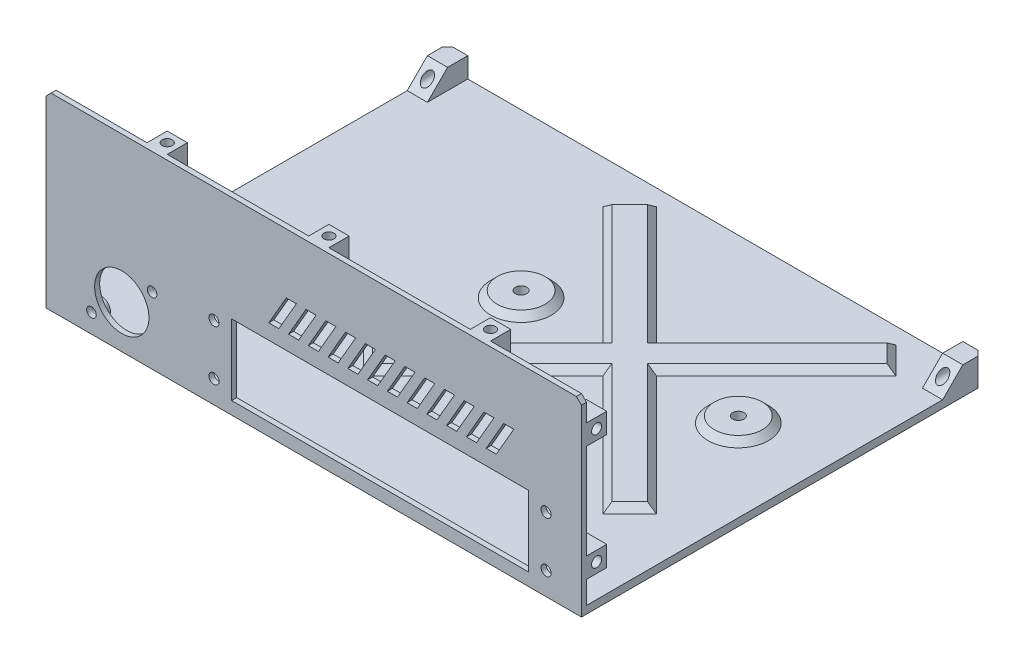
SolidWorks part; units mm, degrees
ref_plane "Płaszczyzna przednia" through (0, 0, 0) normal (0, 0, 1) x (1, 0, 0)
ref_plane "Płaszczyzna górna" through (0, 0, 0) normal (0, 1, 0) x (1, 0, 0)
ref_plane "Płaszczyzna prawa" through (0, 0, 0) normal (1, 0, 0) x (0, 0, -1)
sketch "Szkic1" plane through (0, 0, 0) normal (0, 0, 1) x (1, 0, 0)
  line L1 (0, 0) -> (212, 0)
  line L2 (0, 0) -> (0, 74.66)
  line L3 (0, 74.66) -> (212, 74.66)
  line L4 (212, 0) -> (212, 74.66)
  dimension "D1" = 212
  dimension "D2" = 74.66
extrude "Dodanie-wyciągnięcie1" add sketch "Szkic1" along normal blind 2
ref_plane "Płaszczyzna1" through (106, 0, 0) normal (1, 0, 0) x (0, 0, -1)
sketch "Szkic5" plane through (0, 0, 2) normal (0, 0, 1) x (1, 0, 0)
  line L0 (212, 74.66) -> (0, 74.66) construction
  line L1 (73.5, 33) -> (191, 33)
  line L2 (73.5, 33) -> (73.5, 5)
  line L3 (73.5, 5) -> (191, 5)
  line L4 (191, 33) -> (191, 5)
  line L5 (106, 74.66) -> (106, 105.9064) construction
  line L6 (132.25, 5) -> (132.25, 33) construction
  line L7 (0, 0) -> (212, 0) construction
  line L8 (73.5, 19) -> (191, 19) construction
  line L10 (212, 0) -> (212, 74.66) construction
  circle A5 centre (66.5, 29) radius 2
  circle A6 centre (198, 29) radius 2
  circle A7 centre (198, 9) radius 2
  circle A8 centre (66.5, 9) radius 2
  point P9 (135.25, 19)
  dimension "D6" = 20
  dimension "D4" = 4
  dimension "D7" = 7
  dimension "D1" = 5
  dimension "D2" = 28
  dimension "D3" = 117.5
  dimension "D5" = 21
extrude "Wytnij-wyciągnięcie2" cut sketch "Szkic5" against normal blind 35 contours L2 L3 L4 L1 | A5 | A8 | A6 | A7
sketch "Szkic6" plane through (0, 0, 2) normal (0, 0, 1) x (1, 0, 0)
  line L11 (0, 0) -> (212, 0) construction
  line L12 (0, 74.66) -> (0, 0) construction
  circle A0 centre (30, 17) radius 10.75
  circle A1 centre (42, 26.5) radius 1.9
  circle A2 centre (18, 7.5) radius 1.9
  dimension "D9" = 3.8
  dimension "D10" = 3.8
  dimension "D15" = 21.5
  dimension "D2" = 30
  dimension "D8" = 17
  dimension "D11" = 12
  dimension "D12" = 9.5
  dimension "D13" = 12
  dimension "D14" = 9.5
extrude "Wytnij-wyciągnięcie3" cut sketch "Szkic6" against normal through all
sketch "Szkic8" plane through (0, 0, 0) normal (0, 0, -1) x (-1, 0, 0)
  circle A0 centre (-18, 7.5) radius 3.5
  circle A1 centre (-42, 26.5) radius 3.5
  circle A2 centre (-42, 26.5) radius 2
  circle A3 centre (-18, 7.5) radius 2
  dimension "D1" = 7
  dimension "D2" = 7
  dimension "D3" = 4
  dimension "D4" = 4
extrude "Dodanie-wyciągnięcie4" add sketch "Szkic8" along normal blind 2
ref_plane "Plane1" through (0, 0, 2) normal (1, 0, 0) x (0, 0, -1)
sketch "Sketch2" plane through (0, 0, 0) normal (0, -1, 0) x (1, 0, 0)
  line L5 (0, 0) -> (212, 0)
  line L6 (0, 0) -> (0, -157)
  line L7 (0, -157) -> (212, -157)
  line L8 (212, 0) -> (212, -157)
  line L9 (0, 0) -> (212, -157) construction
  line L10 (0, -157) -> (212, 0) construction
  line L12 (212, 2) -> (212, 0) construction
  point P6 (106, -78.5)
  dimension "D1" = 157
extrude "Boss-Extrude1" add sketch "Sketch2" against normal blind 3
ref_plane "Plane5" through (106, 0, 0) normal (1, 0, 0) x (0, 0, -1)
sketch "Sketch7" plane through (0, 3, 0) normal (0, 1, 0) x (1, 0, 0)
  line L0 (191, 45.1766) -> (183.9289, 38.1056)
  line L1 (191, 45.1766) -> (143.6238, 92.5528)
  line L2 (183.9289, 38.1056) -> (136.5528, 85.4817)
  line L3 (89.1766, 147) -> (82.1056, 139.9289)
  line L4 (183.9289, 147) -> (191, 139.9289)
  line L5 (183.9289, 147) -> (136.5528, 99.6238)
  line L6 (191, 139.9289) -> (143.6238, 92.5528)
  line L7 (82.1056, 45.1766) -> (89.1766, 38.1056)
  line L8 (187.4645, 143.4645) -> (85.6411, 41.6411) construction
  line L9 (187.4645, 41.6411) -> (85.6411, 143.4645) construction
  line L10 (212, 157) -> (212, 0) construction
  line L11 (136.5528, 74.0215) -> (136.5528, 89.2725) construction
  line L12 (111.0017, 92.5528) -> (175.6621, 92.5528) construction
  line L13 (129.4817, 92.5528) -> (82.1056, 139.9289)
  line L14 (136.5528, 85.4817) -> (89.1766, 38.1056)
  line L15 (136.5528, 99.6238) -> (89.1766, 147)
  line L16 (129.4817, 92.5528) -> (82.1056, 45.1766)
  line L18 (0, 157) -> (212, 157) construction
  circle A0 centre (179.5528, 92.5528) radius 9.5
  circle A1 centre (93.5528, 92.5528) radius 9.5
  circle A2 centre (93.5528, 92.5528) radius 2
  circle A3 centre (179.5528, 92.5528) radius 2
  point P12 (136.5528, 92.5528)
  point P13 (136.5528, 92.5528)
  point P15 (0, 0)
  point P27 (0, 0)
  point P28 (184.9485, 21.3587)
  point P33 (180.5723, 24.8942)
  point P34 (-26.6612, 143.6561)
  point P37 (167.6767, 85.5528)
  point P38 (157.1136, 85.5528)
  dimension "D4" = 86
  dimension "D5" = 4
  dimension "D8" = 19
  dimension "D1" = 144
  dimension "D2" = 10
  dimension "D3" = 45
  dimension "D6" = 10
  dimension "D7" = 21
extrude "Boss-Extrude2" add sketch "Sketch7" along normal blind 2.5
chamfer "Chamfer1" distance 2.5 angle 45 14 edges at (93.5528, 3, -102.0528) (179.5528, 3, -102.0528) (187.4645, 3, -143.4645) (167.3119, 3, -116.2409) (167.3119, 3, -68.8647) (187.4645, 3, -41.6411) (160.2409, 3, -61.7936) (112.8647, 3, -61.7936) (85.6411, 3, -41.6411) (105.7936, 3, -68.8647) (105.7936, 3, -116.2409) (85.6411, 3, -143.4645) (112.8647, 3, -123.3119) (160.2409, 3, -123.3119)
sketch "Sketch10" plane through (0, 0, 0) normal (0, -1, 0) x (1, 0, 0)
  circle A0 centre (179.5528, -92.5528) radius 2 construction
  circle A1 centre (93.5528, -92.5528) radius 2 construction
  circle A2 centre (179.5528, -92.5528) radius 2
  circle A3 centre (93.5528, -92.5528) radius 2
  point P0 (179.5528, -92.5528)
  point P2 (93.5528, -92.5528)
hole_wizard "CSK for M4 Hex Socket Countersunk Head Screw1" positions "Sketch10" profile "Sketch11" countersink size "M4" standard "DIN" end condition through all
sketch "Sketch11" plane through (179.5528, 0, -92.5528) normal (1, 0, 0) x (0, 0, -1)
  line L0 (0, 0) -> (0, 74.66)
  line L1 (0, 74.66) -> (2.25, 74.66)
  line L2 (2.25, 74.66) -> (2.25, 2.34)
  line L3 (2.25, 2.34) -> (4.59, 0)
  line L5 (4.59, 0) -> (0, 0)
  line L6 (-2.25, 2.34) -> (-4.59, 0) construction
  line L11 (0, -6.35) -> (0, 107.95) construction
  dimension "Thru Hole Dia." = 4.5
  dimension "Thru Hole Depth" = 74.66
  dimension "Near C'Sink Dia." = 9.18
  dimension "Near C'Sink Angle" = 90
sketch "Sketch13" plane through (0, 74.66, 0) normal (0, 1, 0) x (1, 0, 0)
  line L0 (212, 0) -> (0, 0) construction
  line L1 (110, 0) -> (102, 0)
  line L2 (110, 0) -> (110, 8)
  line L3 (110, 8) -> (102, 8)
  line L4 (102, 0) -> (102, 8)
  line L5 (110, 0) -> (102, 8) construction
  line L6 (110, 8) -> (102, 0) construction
  line L7 (106, -39.963) -> (106, 39.963) construction
  line L8 (0, -60.3) -> (0, 56.3) construction
  line L9 (38, 0) -> (46, 0)
  line L10 (38, 0) -> (38, 8)
  line L11 (38, 8) -> (46, 8)
  line L12 (46, 0) -> (46, 8)
  line L13 (38, 0) -> (46, 8) construction
  line L14 (38, 8) -> (46, 0) construction
  line L15 (174, 0) -> (166, 0)
  line L16 (174, 8) -> (166, 0) construction
  line L17 (174, 0) -> (166, 8) construction
  line L18 (166, 0) -> (166, 8)
  line L19 (174, 0) -> (174, 8)
  line L20 (174, 8) -> (166, 8)
  circle A0 centre (106, 4) radius 2
  circle A1 centre (42, 4) radius 2
  circle A2 centre (170, 4) radius 2
  point P4 (106, 4)
  point P16 (42, 4)
  point P26 (170, 4)
  dimension "D1" = 4
  dimension "D4" = 4
  dimension "D2" = 8
  dimension "D3" = 8
  dimension "D5" = 38
extrude "Boss-Extrude3" add sketch "Sketch13" against normal blind 8
sketch "Sketch15" plane through (0, 0, -157) normal (0, 0, -1) x (-1, 0, 0)
  line L0 (-106, 41.063) -> (-106, -41.063) construction
  line L1 (-212, 3) -> (-204, 3)
  line L2 (-212, 3) -> (-212, 11)
  line L3 (-212, 11) -> (-204, 11)
  line L4 (-204, 3) -> (-204, 11)
  line L5 (-212, 3) -> (-204, 11) construction
  line L6 (-212, 11) -> (-204, 3) construction
  line L7 (0, 11) -> (-8, 3) construction
  line L8 (0, 3) -> (-8, 11) construction
  line L9 (-8, 3) -> (-8, 11)
  line L10 (0, 11) -> (-8, 11)
  line L11 (0, 3) -> (0, 11)
  line L12 (0, 3) -> (-8, 3)
  circle A0 centre (-208, 7) radius 2
  circle A1 centre (-4, 7) radius 2
  point P4 (-208, 7)
  point P16 (-4, 7)
  dimension "D2" = 4
  dimension "D1" = 8
extrude "Boss-Extrude4" add sketch "Sketch15" against normal blind 8
chamfer "Chamfer3" distance 8 angle 45 2 edges at (4, 3, -149) (208, 3, -149)
chamfer "Chamfer4" distance 2 angle 45 4 edges at (0, 5.5, -157) (212, 5.5, -157) (0, 74.66, 1) (212, 74.66, 1)
sketch "Sketch16" plane through (212, 0, 0) normal (1, 0, 0) x (0, 0, -1)
  line L0 (0, 3) -> (0, 72.66) construction
  line L1 (0, 65.58) -> (8, 65.58)
  line L2 (0, 65.58) -> (0, 57.58)
  line L3 (0, 57.58) -> (8, 57.58)
  line L4 (8, 65.58) -> (8, 57.58)
  line L5 (0, 65.58) -> (8, 57.58) construction
  line L6 (0, 57.58) -> (8, 65.58) construction
  line L7 (0, 23) -> (0, 30) construction
  line L8 (0, 19.9518) -> (8, 19.9518)
  line L9 (0, 19.9518) -> (0, 11.9518)
  line L10 (0, 11.9518) -> (8, 11.9518)
  line L11 (8, 19.9518) -> (8, 11.9518)
  line L12 (0, 19.9518) -> (8, 11.9518) construction
  line L13 (0, 11.9518) -> (8, 19.9518) construction
  line L14 (33.9, 55.9948) -> (-2, 55.9948) construction
  line L15 (-2, 67.1652) -> (33.9, 67.1652) construction
  line L16 (-2, 21.1652) -> (33.9, 21.1652) construction
  line L17 (34.6686, 10.7385) -> (-2, 10.7385) construction
  line L18 (33.9, 55.9948) -> (-2, 55.9948) construction
  line L19 (-2, 67.1652) -> (33.9, 67.1652) construction
  line L20 (-2, 21.1652) -> (33.9, 21.1652) construction
  line L21 (34.6686, 10.7385) -> (-2, 10.7385) construction
  line L22 (4, 67.1652) -> (4, 55.9948) construction
  line L23 (4, 10.7385) -> (4, 21.1652) construction
  circle A0 centre (4, 61.58) radius 2
  circle A1 centre (4, 15.9518) radius 2
  point P4 (4, 61.58)
  point P11 (4, 15.9518)
  point P30 (4, 61.58)
  point P31 (0, 0)
  point P32 (4, 15.9518)
  dimension "D2" = 4
  dimension "D3" = 4
  dimension "D1" = 8
extrude "Boss-Extrude5" add sketch "Sketch16" against normal blind 8
mirror "Mirror1" about plane through (106, 0, 0) normal (1, 0, 0) of "Boss-Extrude5"
sketch "Sketch17" plane through (0, 0, 2) normal (0, 0, 1) x (1, 0, 0)
  line L4 (88.2028, 45.7) -> (88.2028, 36.7)
  line L5 (89.7028, 35.2) -> (183.7028, 35.2)
  line L6 (185.2028, 36.7) -> (185.2028, 45.7)
  line L7 (183.7028, 47.2) -> (89.7028, 47.2)
  line L8 (88.2028, 45.7) -> (88.2028, 36.7)
  line L9 (89.7028, 35.2) -> (183.7028, 35.2)
  line L10 (185.2028, 36.7) -> (185.2028, 45.7)
  line L11 (183.7028, 47.2) -> (89.7028, 47.2)
  arc A4 (89.7028, 47.2) -> (88.2028, 45.7) centre (89.7028, 45.7) ccw
  arc A5 (88.2028, 36.7) -> (89.7028, 35.2) centre (89.7028, 36.7) ccw
  arc A6 (183.7028, 35.2) -> (185.2028, 36.7) centre (183.7028, 36.7) ccw
  arc A7 (185.2028, 45.7) -> (183.7028, 47.2) centre (183.7028, 45.7) ccw
  arc A8 (89.7028, 47.2) -> (88.2028, 45.7) centre (89.7028, 45.7) ccw
  arc A9 (88.2028, 36.7) -> (89.7028, 35.2) centre (89.7028, 36.7) ccw
  arc A10 (183.7028, 35.2) -> (185.2028, 36.7) centre (183.7028, 36.7) ccw
  arc A11 (185.2028, 45.7) -> (183.7028, 47.2) centre (183.7028, 45.7) ccw
  dimension "D1" = 0
sketch "Sketch18" plane through (0, 0, 2) normal (0, 0, 1) x (1, 0, 0)
  line L0 (88.2028, 39) -> (88.2028, 51) construction
  line L1 (185.2028, 39) -> (185.2028, 51) construction
  line L2 (185.2028, 51) -> (88.2028, 51) construction
  line L3 (88.2028, 39) -> (185.2028, 39) construction
  line L8 (73.5, 33) -> (191, 33) construction
  line L9 (88.2028, 45.7) -> (88.2028, 36.7) construction
  line L10 (185.2028, 36.7) -> (185.2028, 45.7) construction
  line L11 (88.2028, 39) -> (95.131, 51)
  line L12 (95.131, 51) -> (99.131, 51)
  line L13 (99.131, 51) -> (92.2028, 39)
  line L14 (92.2028, 39) -> (88.2028, 39)
  line L15 (100.0275, 39) -> (96.0275, 39)
  line L16 (96.0275, 39) -> (102.9557, 51)
  line L17 (102.9557, 51) -> (106.9557, 51)
  line L18 (106.9557, 51) -> (100.0275, 39)
  line L19 (107.8522, 39) -> (103.8522, 39)
  line L20 (103.8522, 39) -> (110.7804, 51)
  line L21 (110.7804, 51) -> (114.7804, 51)
  line L22 (114.7804, 51) -> (107.8522, 39)
  line L23 (115.6769, 39) -> (111.6769, 39)
  line L24 (111.6769, 39) -> (118.6051, 51)
  line L25 (118.6051, 51) -> (122.6051, 51)
  line L26 (122.6051, 51) -> (115.6769, 39)
  line L27 (123.5016, 39) -> (119.5016, 39)
  line L28 (119.5016, 39) -> (126.4298, 51)
  line L29 (126.4298, 51) -> (130.4298, 51)
  line L30 (130.4298, 51) -> (123.5016, 39)
  line L31 (131.3263, 39) -> (127.3263, 39)
  line L32 (127.3263, 39) -> (134.2545, 51)
  line L33 (134.2545, 51) -> (138.2545, 51)
  line L34 (138.2545, 51) -> (131.3263, 39)
  line L35 (139.151, 39) -> (135.151, 39)
  line L36 (135.151, 39) -> (142.0792, 51)
  line L37 (142.0792, 51) -> (146.0792, 51)
  line L38 (146.0792, 51) -> (139.151, 39)
  line L39 (146.9757, 39) -> (142.9757, 39)
  line L40 (142.9757, 39) -> (149.9039, 51)
  line L41 (149.9039, 51) -> (153.9039, 51)
  line L42 (153.9039, 51) -> (146.9757, 39)
  line L43 (154.8004, 39) -> (150.8004, 39)
  line L44 (150.8004, 39) -> (157.7287, 51)
  line L45 (157.7287, 51) -> (161.7287, 51)
  line L46 (161.7287, 51) -> (154.8004, 39)
  line L47 (162.6252, 39) -> (158.6252, 39)
  line L48 (158.6252, 39) -> (165.5534, 51)
  line L49 (165.5534, 51) -> (169.5534, 51)
  line L50 (169.5534, 51) -> (162.6252, 39)
  line L51 (170.4499, 39) -> (166.4499, 39)
  line L52 (166.4499, 39) -> (173.3781, 51)
  line L53 (173.3781, 51) -> (177.3781, 51)
  line L54 (177.3781, 51) -> (170.4499, 39)
  line L55 (178.2746, 39) -> (174.2746, 39)
  line L56 (174.2746, 39) -> (181.2028, 51)
  line L57 (181.2028, 51) -> (185.2028, 51)
  line L58 (185.2028, 51) -> (178.2746, 39)
  point P5 (0, 0)
  dimension "D1" = 6
  dimension "D2" = 12
  dimension "D3" = 60
  dimension "D4" = 4
extrude "Cut-Extrude1" cut sketch "Sketch18" against normal up to next
